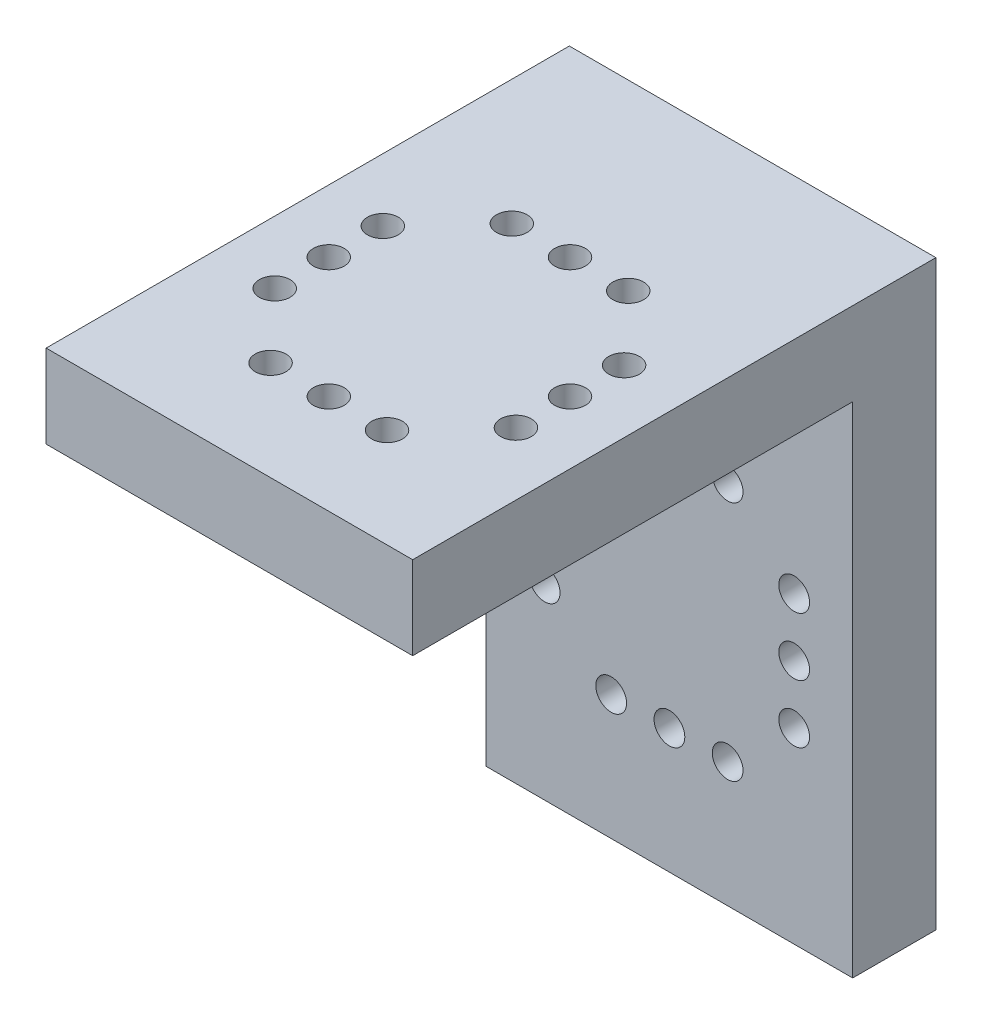
SolidWorks part; units mm, degrees
ref_plane "Спереди" through (0, 0, 0) normal (0, 0, 1) x (1, 0, 0)
ref_plane "Сверху" through (0, 0, 0) normal (0, 1, 0) x (1, 0, 0)
ref_plane "Справа" through (0, 0, 0) normal (1, 0, 0) x (0, 0, -1)
sketch "Эскиз1" plane through (0, 0, 0) normal (0, 1, 0) x (1, 0, 0)
  line L0 (0, 0) -> (0, 4080.4203) construction
  line L1 (0, 4080.4203) -> (0, -5373.225) construction
  line L2 (0, 0) -> (-5563.7687, 0) construction
  line L3 (0, 0) -> (2771.6705, 0) construction
  line L4 (0, 7.25) -> (-19.2559, 7.25) construction
  line L5 (0, 7.25) -> (25.1342, 7.25) construction
  line L6 (-7.25, 0) -> (-7.25, -6.5) construction
  line L8 (11.0165, -13.2246) -> (-11.0165, -13.2246)
  line L9 (11.0165, -13.2246) -> (11.0165, 13.2246)
  line L10 (11.0165, 13.2246) -> (-11.0165, 13.2246)
  line L11 (-11.0165, -13.2246) -> (-11.0165, 13.2246)
  line L12 (11.0165, -13.2246) -> (-11.0165, 13.2246) construction
  line L13 (11.0165, 13.2246) -> (-11.0165, -13.2246) construction
  line L14 (-11.0165, 13.2246) -> (11.0165, 13.2246)
  line L15 (-11.0165, 13.2246) -> (-11.0165, 18.2246)
  line L16 (-11.0165, 18.2246) -> (11.0165, 18.2246)
  line L17 (11.0165, 13.2246) -> (11.0165, 18.2246)
  circle A0 centre (0, 7.25) radius 0.925
  circle A1 centre (-3.5, 7.25) radius 0.925
  circle A2 centre (3.5, 7.25) radius 0.925
  circle A3 centre (3.5, -7.25) radius 0.925
  circle A4 centre (0, -7.25) radius 0.925
  circle A5 centre (-3.5, -7.25) radius 0.925
  circle A6 centre (-7.25, 0) radius 0.925
  circle A7 centre (-7.25, -3.25) radius 0.925
  circle A8 centre (-7.25, 3.25) radius 0.925
  circle A9 centre (7.25, 3.25) radius 0.925
  circle A10 centre (7.25, 0) radius 0.925
  circle A11 centre (7.25, -3.25) radius 0.925
  dimension "D1" = 1.85
  dimension "D2" = 1.85
  dimension "D4" = 1.85
  dimension "D6" = 1.85
  dimension "D3" = 3.5
  dimension "D5" = 7.25
  dimension "D7" = 3.25
  dimension "D8" = 7.25
  dimension "D9" = 5
extrude "Бобышка-Вытянуть1" add sketch "Эскиз1" against normal blind 5 contours L11 L8 L9 L10 A10 A9 A5 A2 A1 A0 A3 A4 A6 A7 A8 A11 region at (0, 0, 0)
extrude "Бобышка-Вытянуть2" add sketch "Эскиз1<3>" against normal blind 35 contours L10 L17 L16 L15 region at (0, 0, -15.7246)
sketch "Эскиз1<3>" plane through (0, 0, 0) normal (0, 1, 0) x (1, 0, 0) same geometry as "Эскиз1"
sketch "Эскиз3" plane through (0, 0, -13.2246) normal (0, 0, 1) x (1, 0, 0)
  line L0 (0, -5) -> (0, -35) construction
  line L1 (11.0165, -5) -> (-11.0165, -5) construction
  line L2 (11.0165, -35) -> (-11.0165, -35) construction
  line L3 (0, -13) -> (9.7894, -13) construction
  line L4 (0, -13) -> (-10.3168, -13) construction
  line L5 (0, -20.25) -> (-10.0693, -20.25) construction
  line L6 (0, -20.25) -> (9.2879, -20.25) construction
  line L7 (-7.5, -20.25) -> (-7.5, -13.7739) construction
  circle A0 centre (0, -13) radius 0.925
  circle A1 centre (-3.5, -13) radius 0.925
  circle A2 centre (3.5, -13) radius 0.925
  circle A3 centre (3.5, -27.5) radius 0.925
  circle A4 centre (0, -27.5) radius 0.925
  circle A5 centre (-3.5, -27.5) radius 0.925
  circle A6 centre (-7.5, -20.25) radius 0.925
  circle A7 centre (-7.5, -16.75) radius 0.925
  circle A8 centre (-7.5, -23.75) radius 0.925
  circle A9 centre (7.5, -16.75) radius 0.925
  circle A10 centre (7.5, -20.25) radius 0.925
  circle A11 centre (7.5, -23.75) radius 0.925
  point P28 (0, 0)
  point P29 (0, 0)
  point P32 (0, 0)
  point P33 (0, 0)
  dimension "D1" = 1.85
  dimension "D3" = 1.85
  dimension "D6" = 1.85
  dimension "D7" = 1.85
  dimension "D2" = 8
  dimension "D4" = 3.5
  dimension "D5" = 7.25
  dimension "D8" = 3.5
  dimension "D9" = 7.5
extrude "Вырез-Вытянуть1" cut sketch "Эскиз3" against normal blind 25
